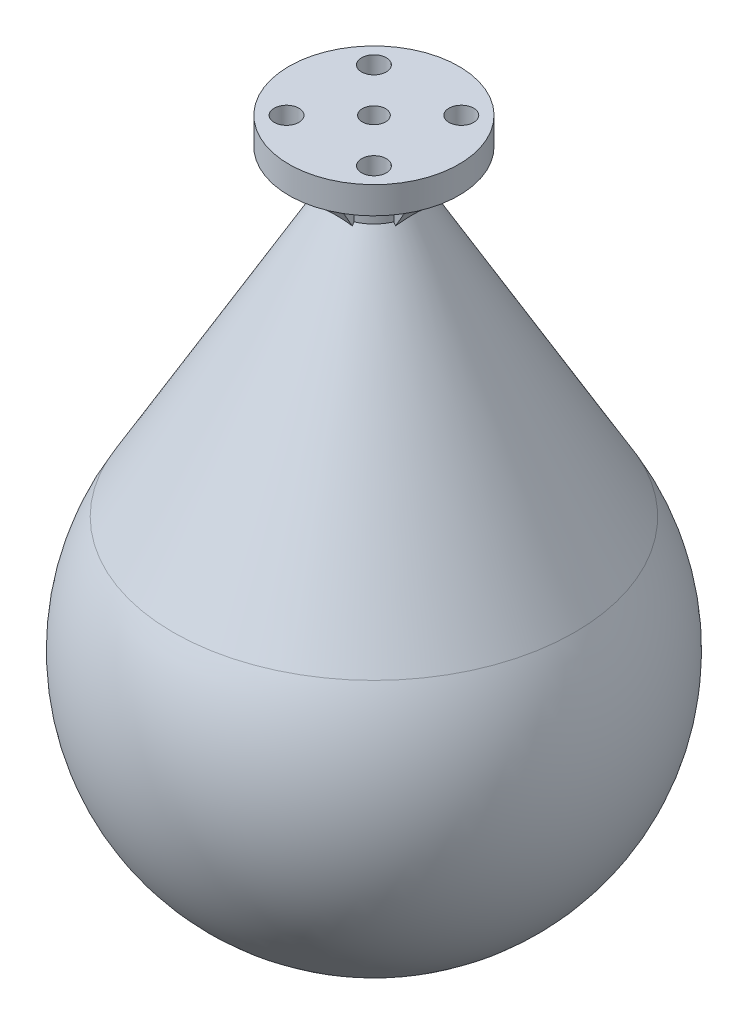
SolidWorks part; units mm, degrees
ref_plane "前视基准面" through (0, 0, 0) normal (0, 0, 1) x (1, 0, 0)
ref_plane "上视基准面" through (0, 0, 0) normal (0, 1, 0) x (1, 0, 0)
ref_plane "右视基准面" through (0, 0, 0) normal (1, 0, 0) x (0, 0, -1)
sketch "草图2" plane through (0, 0, 0) normal (0, 0, 1) x (1, 0, 0)
  line L1 (5, 51.3397) -> (25.9808, 15)
  line L3 (11, 60) -> (11, 56.5)
  line L4 (11, 56.5) -> (5, 56.5)
  line L7 (5, 56.5) -> (5, 51.3397)
  line L8 (1.9689, 49.5897) -> (22.9497, 13.25)
  line L9 (1.9689, 49.5897) -> (1.5, 50.4019)
  line L10 (0, -26.5) -> (0, -30)
  line L11 (1.5, 60) -> (1.5, 50.4019)
  line L12 (11, 60) -> (1.5, 60)
  arc A0 (0, -30) -> (25.9808, 15) centre (0, 0) ccw
  arc A1 (0, -26.5) -> (22.9497, 13.25) centre (0, 0) ccw
  dimension "D1" = 3.5
revolve "旋转1" add sketch "草图2" angle 360 about L10
sketch "草图3" plane through (0, 60, 0) normal (0, 1, 0) x (1, 0, 0)
  circle A1 centre (-5.6569, 5.6569) radius 1.6
  circle A2 centre (5.6569, 5.6569) radius 1.6
  circle A3 centre (5.6569, -5.6569) radius 1.6
  circle A4 centre (-5.6569, -5.6569) radius 1.6
  point P12 (0, 0)
  dimension "D1" = 4
extrude "切除-拉伸1" cut sketch "草图3" against normal up to next
sketch "草图4" plane through (0, 0, 0) normal (0, 0, 1) x (1, 0, 0)
  line L0 (-5, 51.3397) -> (-7.9793, 56.5)
  line L1 (-5, 51.3397) -> (5, 51.3397) construction
  line L2 (-5, 56.5) -> (-5, 51.3397) construction
  line L6 (-11, 56.5) -> (11, 56.5) construction
  line L7 (-7.9793, 56.5) -> (-8.5201, 57.4368)
  line L8 (-8.5201, 57.4368) -> (-4.1219, 57.4368)
  line L9 (-4.1219, 57.4368) -> (-4.1219, 49.8188)
  line L10 (-5, 51.3397) -> (-4.1219, 49.8188)
extrude "凸台-拉伸1" add sketch "草图4" along normal blind 2 and the other way blind 2 contours L0 L7 L8 L9 L10
pattern_circular "阵列(圆周)1" count 4 every 90 about axis through (0, 60, 0) along (0, 1, 0) of "凸台-拉伸1"
